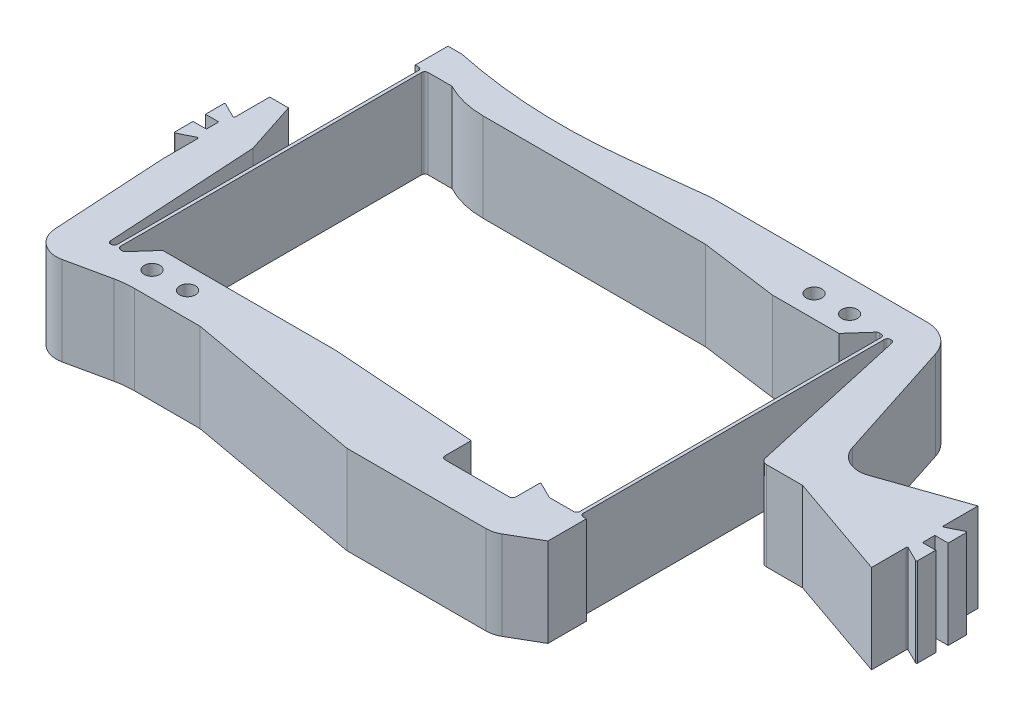
SolidWorks part; units mm, degrees
material "6061-O (SS)"
ref_plane "Front Plane" through (0, 0, 0) normal (0, 0, 1) x (1, 0, 0)
ref_plane "Top Plane" through (0, 0, 0) normal (0, 1, 0) x (1, 0, 0)
ref_plane "Right Plane" through (0, 0, 0) normal (1, 0, 0) x (0, 0, -1)
sketch "Sketch1" plane through (0, 0, 0) normal (0, 1, 0) x (1, 0, 0)
  line L1 (-76.2, 0) -> (76.2, 0) construction
  line L7 (0, 43.9941) -> (-76.2, 0) construction
  line L8 (76.2, 0) -> (0, 43.9941) construction
  line L9 (-43.0927, 22) -> (-43.0927, -22) construction
  line L10 (9.8199, -19.0502) -> (-29.8041, -19.0502)
  line L11 (9.8199, -19.0502) -> (9.8199, 19.0502)
  line L12 (9.8199, 19.0502) -> (-29.8041, 19.0502)
  line L13 (-29.8041, -19.0502) -> (-29.8041, 19.0502)
  line L14 (9.8199, -19.0502) -> (-29.8041, 19.0502) construction
  line L15 (9.8199, 19.0502) -> (-29.8041, -19.0502) construction
  line L16 (-29.8041, 19.0502) -> (-39.3291, 19.0502)
  line L17 (-29.8041, 19.0502) -> (-29.8041, -19.0502)
  line L18 (-29.8041, -19.0502) -> (-39.3291, -19.0502)
  line L19 (-39.3291, 19.0502) -> (-39.3291, -19.0502)
  line L20 (9.8199, -19.0502) -> (19.3449, -19.0502)
  line L21 (9.8199, -19.0502) -> (9.8199, 19.0502)
  line L22 (9.8199, 19.0502) -> (19.3449, 19.0502)
  line L23 (19.3449, -19.0502) -> (19.3449, 19.0502)
  line L24 (23.1085, 22) -> (23.1085, -22) construction
  line L25 (-43.3213, 22) -> (-43.3213, -22)
  line L26 (22.8799, 22) -> (22.8799, -22)
  line L27 (-42.8641, 22) -> (-42.8641, -22)
  line L28 (23.3371, 22) -> (23.3371, -22)
  line L29 (-42.8641, -5.4114) -> (-39.3291, -5.4114) construction
  line L30 (22.8799, -5.4114) -> (19.3449, -5.4114) construction
  line L31 (0, 0) -> (0, 43.9941) construction
  line L32 (-52.8845, 13.4612) -> (-51.8236, 31.3444) construction
  line L33 (-51.8236, 31.3444) -> (-30.0207, 26.6616) construction
  line L34 (-45.0888, 7.62) -> (-45.0888, -7.62) construction
  line L35 (-44.2357, 22) -> (-43.3213, 22)
  line L36 (-50.6866, 7.62) -> (-49.4633, 28.2396)
  line L37 (-49.4633, 28.2396) -> (-19.3998, 21.7826)
  line L38 (-49.4633, 28.2396) -> (-30.5541, 24.1783) construction
  line L39 (52.8845, 13.4612) -> (36.8667, 5.4384) construction
  line L40 (36.8667, 5.4384) -> (30.0207, 26.6616) construction
  line L41 (0, 43.9941) -> (-30.0207, 26.6616) construction
  line L42 (53.8514, 11.5308) -> (35.5843, 2.3813)
  line L43 (35.5843, 2.3813) -> (27.9659, 25.9988)
  line L44 (24.2515, 22) -> (28.7842, 23.4621) construction
  line L45 (35.5843, 2.3813) -> (35.5843, -2.3813) construction
  line L46 (-44.2357, 22) -> (-45.0888, 7.62)
  line L47 (-45.0888, -7.62) -> (-44.2357, -22)
  line L48 (-50.349, 13.3108) -> (-49.4633, 28.2396) construction
  line L49 (53.8514, -11.5308) -> (35.5843, -2.3813)
  line L50 (-43.3213, -22) -> (-44.2357, -22)
  line L52 (35.5843, -2.3813) -> (27.9659, -25.9988)
  line L53 (-49.4633, -28.2396) -> (-19.3998, -21.7826)
  line L54 (-50.6866, -7.62) -> (-49.4633, -28.2396)
  line L55 (23.3371, 22) -> (24.2515, 22)
  line L56 (76.2, 0) -> (0, -43.9941) construction
  line L57 (0, -43.9941) -> (-76.2, 0) construction
  line L58 (71.882, 0) -> (0, -41.5011)
  line L59 (0, -41.5011) -> (-71.882, 0)
  line L60 (0, 41.5011) -> (-71.882, 0)
  line L61 (71.882, 0) -> (0, 41.5011)
  line L62 (27.5523, -28.2396) -> (-2.5112, -21.7826)
  line L63 (27.5523, 28.2396) -> (-2.5112, 21.7826)
  circle A0 centre (-43.0927, 22) radius 4.7627 construction
  circle A3 centre (24.2515, 22) radius 4.7627 construction
  point P2 (0, 0)
  point P12 (-9.9921, 0)
  point P46 (35.5843, 0)
  point P47 (0, 43.9941)
  point P57 (0, 43.9941)
  point P64 (-45.0888, 0)
  point P70 (-43.3213, 0)
  point P77 (-10.9555, 0)
  dimension "D4" = 38.1004
  dimension "D5" = 39.624
  dimension "D6" = 9.525
  dimension "D7" = 44
  dimension "D8" = 150
  dimension "D13" = 1.7675
  dimension "D2" = 152.4
  dimension "D19" = 0.9144
  dimension "D14" = 5.588
  dimension "D15" = 15.24
  dimension "D3" = 4.7627
  dimension "D11" = 3.535
  dimension "D9" = 0.2286
  dimension "D18" = 2.159
  dimension "D17" = 2.159
  dimension "D16" = 2
  dimension "D20" = 2
sketch "Sketch2" plane through (0, 0, 0) normal (0, 1, 0) x (1, 0, 0)
  line L3 (-29.8041, -19.0502) -> (-29.8041, 19.0502) construction
  line L7 (9.8199, 19.0502) -> (19.3449, 19.0502)
  line L10 (-50.6806, 7.62) -> (-47.9942, 7.62)
  line L11 (-47.9942, 7.62) -> (-45.5383, 0.0647)
  line L12 (-45.5383, 0.0647) -> (-44.2357, -22)
  line L13 (-44.2357, -22) -> (-41.9497, -22)
  line L14 (-41.9497, -22) -> (-39.3291, -19.0502)
  line L24 (-30.1531, 24.0922) -> (-6.6386, 26.7627)
  line L25 (-39.3291, -19.0502) -> (-14.5241, -19.0502)
  line L26 (9.8199, -19.0502) -> (-29.8041, -19.0502) construction
  line L29 (9.8199, 19.0502) -> (-1.2291, 20.5502)
  line L30 (9.8199, 19.0502) -> (-29.8041, 19.0502) construction
  line L32 (16.4949, -22) -> (29.7221, -22) construction
  line L34 (71.882, 0) -> (0, -41.5011) construction
  line L36 (0, -41.5011) -> (-71.882, 0) construction
  line L37 (-34.5666, -6.7134) -> (-34.5666, -25.7742) construction
  line L38 (-37.9845, -25.7742) -> (-49.4633, -28.2396)
  line L39 (-49.4633, -28.2396) -> (-50.6806, -7.62)
  line L40 (-50.6806, -7.62) -> (-50.6806, 7.62)
  line L43 (-49.4633, 28.2396) -> (-19.3998, 21.7826) construction
  line L44 (-42.2453, 26.6893) -> (-30.1531, 24.0922)
  line L45 (0, 41.5011) -> (-71.882, 0) construction
  line L47 (28.7842, 23.4621) -> (35.5843, 2.3813)
  line L48 (35.5843, 2.3813) -> (50.6806, 7.62)
  line L49 (-6.6386, 26.7627) -> (24.2515, 26.7627)
  line L51 (-39.3291, -6.7134) -> (-29.8041, -6.7134) construction
  line L52 (50.6806, -7.62) -> (35.5843, -2.3813)
  line L53 (35.5843, -2.3813) -> (29.6871, -2.3813)
  line L54 (29.6871, -2.3813) -> (24.2515, 22)
  line L55 (24.2515, 22) -> (21.9655, 22)
  line L61 (19.2496, -30.3873) -> (-1.6246, -30.3873)
  line L64 (-1.2291, 20.5502) -> (-36.4963, 20.5502)
  line L68 (-42.2453, 26.6893) -> (-48.2113, 26.6893)
  line L69 (-1.6246, -30.3873) -> (-27.2398, -25.7742)
  line L70 (-38.9574, 22) -> (-36.4963, 20.5502)
  line L71 (16.4949, -22) -> (16.4949, -24.7993)
  line L73 (21.9655, 22) -> (19.3449, 19.0502)
  line L74 (16.4949, -24.7993) -> (6.3199, -24.7993)
  line L75 (6.3199, -24.7993) -> (6.3199, -20.5502)
  line L76 (6.3199, -20.5502) -> (-14.5241, -19.0502)
  line L77 (19.2496, -30.3873) -> (29.7221, -24.341)
  line L78 (9.8199, -19.0502) -> (12.9949, -19.0502) construction
  line L79 (9.8199, -19.0502) -> (9.8199, -23.7833) construction
  line L80 (9.8199, -23.7833) -> (12.9949, -23.7833) construction
  line L81 (12.9949, -19.0502) -> (12.9949, -23.7833) construction
  line L82 (29.7221, -24.341) -> (29.7221, -22)
  line L83 (0, 0) -> (0, 13.8808) construction
  line L84 (50.6806, -7.62) -> (50.6806, 7.62)
  line L85 (-37.9845, -25.7742) -> (-27.2398, -25.7742)
  line L86 (-39.3291, 19.0502) -> (-39.3291, -19.0502) construction
  line L87 (-49.4633, -28.2396) -> (-19.3998, -21.7826) construction
  line L90 (9.8199, 19.0502) -> (-29.8041, -19.0502) construction
  line L91 (-38.9574, 22) -> (-48.2113, 22)
  line L92 (-48.2113, 26.6893) -> (-48.2113, 22)
  line L95 (-76.2, 0) -> (76.2, 0) construction
  line L96 (16.4949, -22) -> (16.4949, -20.7842)
  line L97 (23.3371, 22) -> (23.3371, -22) construction
  line L99 (16.4949, -20.7842) -> (18.9624, -22)
  line L100 (29.7221, -22) -> (18.9624, -22)
  circle A0 centre (24.2515, 22) radius 4.7627 construction
  arc A1 (24.2515, 26.7627) -> (28.7842, 23.4621) centre (24.2515, 22) cw
  circle A2 centre (-41.9497, -22) radius 4.5227 construction
  circle A3 centre (-44.2357, -22) radius 5.5863 construction
  point P10 (23.1085, 22)
  point P19 (50.6806, 0)
  point P44 (-43.0927, -22)
  point P50 (23.1085, -22)
  point P51 (-9.9921, 0)
  point P112 (-9.9514, 0)
  dimension "D2" = 9.0453
  dimension "D4" = 11.1726
  dimension "D1" = 28.575
  dimension "D5" = 3.5
  dimension "D6" = 3.5
  dimension "D7" = 3.175
  dimension "D8" = 5.588
  dimension "D9" = 1.016
  dimension "D10" = 1.5
  dimension "D3" = 9.525
  dimension "D11" = 9.525
  dimension "D13" = 57.15
  dimension "D12" = 1.5
  dimension "D15" = 25.5194
  dimension "D14" = 2.4675
  dimension "D16" = 6.35
extrude "Boss-Extrude1" add sketch "Sketch2" along normal blind 6.35 and the other way blind 6.35
sketch "Sketch3" plane through (0, 0, 0) normal (0, 1, 0) x (1, 0, 0)
  line L0 (-42.8641, 22) -> (-42.8641, -22) construction
  line L1 (-42.8641, 22.508) -> (-43.3213, 22.508)
  line L2 (-42.8641, 22.508) -> (-42.8641, -22)
  line L3 (-42.8641, -22) -> (-43.3213, -22)
  line L4 (-43.3213, 22.508) -> (-43.3213, -22)
  line L5 (22.8799, -22) -> (23.3371, -22)
  line L6 (22.8799, -22) -> (22.8799, 22.508)
  line L7 (22.8799, 22.508) -> (23.3371, 22.508)
  line L8 (23.3371, -22) -> (23.3371, 22.508)
  line L9 (23.3371, 22) -> (23.3371, -22) construction
  line L10 (-48.2113, 22) -> (-38.9574, 22) construction
  dimension "D1" = 0.508
extrude "Boss-Extrude2" add sketch "Sketch3" along normal through all and the other way through all
sketch "Sketch7" plane through (0, 0, 0) normal (0, 1, 0) x (1, 0, 0)
  line L0 (-50.6806, 0) -> (-50.6806, 2.54) construction
  line L1 (-50.6806, 7.62) -> (-50.6806, -7.62) construction
  line L2 (-50.6806, 2.54) -> (-53.2206, 3.81) construction
  line L3 (-53.2206, 3.81) -> (-53.2206, -3.81) construction
  line L4 (-53.2206, -3.81) -> (-50.6806, -2.54) construction
  line L5 (-50.6806, -2.54) -> (-50.6806, 0) construction
  line L6 (0, 0) -> (0, 12.9706) construction
  line L7 (-76.2, 0) -> (76.2, 0) construction
  line L8 (0, 0) -> (0, 43.9941) construction
  line L14 (-53.1444, 3.6867) -> (-53.1444, -3.6867)
  line L15 (-53.1444, -3.6867) -> (-50.7568, -2.4929)
  line L16 (-50.7568, -2.4929) -> (-50.7568, 0) construction
  line L17 (-50.7568, 0) -> (-50.7568, 2.4929) construction
  line L18 (-50.7568, 2.4929) -> (-53.1444, 3.6867)
  line L19 (-50.7568, 2.4929) -> (-50.6806, 2.4548)
  line L20 (-50.6806, 2.4548) -> (-50.6806, -2.4548)
  line L21 (-50.6806, -2.4548) -> (-50.7568, -2.4929)
  line L22 (50.6806, 2.4548) -> (50.6806, -2.4548)
  line L23 (50.7568, 2.4929) -> (50.6806, 2.4548)
  line L24 (50.7568, 2.4929) -> (53.1444, 3.6867)
  line L25 (53.1444, 3.6867) -> (53.1444, -3.6867)
  line L26 (53.1444, -3.6867) -> (50.7568, -2.4929)
  line L27 (50.6806, -2.4548) -> (50.7568, -2.4929)
  dimension "D1" = 2.54
  dimension "D2" = 7.62
  dimension "D3" = 2.54
  dimension "D4" = 0.0762
extrude "Boss-Extrude4" add sketch "Sketch7" along normal through all and the other way through all
sketch "Sketch8" plane through (0, 6.35, 0) normal (0, 1, 0) x (1, 0, 0)
  line L0 (-76.2, 0) -> (76.2, 0) construction
  line L1 (-51.2394, -0.889) -> (-53.2714, -0.889)
  line L2 (-51.2394, -0.889) -> (-51.2394, 0.889)
  line L3 (-51.2394, 0.889) -> (-53.2714, 0.889)
  line L4 (-53.2714, -0.889) -> (-53.2714, 0.889)
  line L5 (-51.2394, -0.889) -> (-53.2714, 0.889) construction
  line L6 (-51.2394, 0.889) -> (-53.2714, -0.889) construction
  line L7 (-53.1444, 3.6867) -> (-53.1444, -3.6867) construction
  line L8 (0, 0) -> (0, 15.7634) construction
  line L9 (0, 0) -> (0, 43.9941) construction
  line L10 (51.2394, 0.889) -> (53.2714, -0.889) construction
  line L11 (51.2394, -0.889) -> (53.2714, 0.889) construction
  line L12 (53.2714, -0.889) -> (53.2714, 0.889)
  line L13 (51.2394, 0.889) -> (53.2714, 0.889)
  line L14 (51.2394, -0.889) -> (51.2394, 0.889)
  line L15 (51.2394, -0.889) -> (53.2714, -0.889)
  point P0 (-52.2554, 0)
  point P18 (52.2554, 0)
  dimension "D1" = 2.032
  dimension "D2" = 1.778
  dimension "D3" = 0.127
extrude "Cut-Extrude1" cut sketch "Sketch8" against normal through all
fillet "Fillet1" radius 0.4572 12 edges at (24.2515, 0, -22) (21.9655, 0, -22) (-41.9497, 0, 22) (-42.8641, 0, 22) (-44.2357, 0, 22) (-43.3213, 0, 22) (23.3371, 0, -22) (22.8799, 0, -22) (-42.8641, 0, -22) (-43.3213, 0, -22) (23.3371, 0, 22) (22.8799, 0, 22)
fillet "Fillet2" radius 0.9144 5 edges at (29.6871, 0, 2.3813) (29.7221, 0, 22) (29.7221, 0, 24.341) (-48.2113, 0, -26.6893) (-48.2113, 0, -22)
fillet "Fillet3" radius 3.556 3 edges at (35.5843, 0, -2.3813) (-49.4633, 0, 28.2396) (19.2496, 0, 30.3873)
fillet "Fillet6" radius 12.7 2 edges at (-36.4963, 0, -20.5502) (-37.9845, 0, 25.7742)
ref_axis "Axis2" through (0, 0, -43.9941) along (0, 1, 0)
pattern_circular "CirPattern3" [suppressed] count 3 over 360 about axis through (0, 0, -43.9941) along (0, 1, 0) of bodies 145 106
ref_axis "Axis3" through (-76.2, 0, 0) along (0, 1, 0)
pattern_circular "CirPattern4" [suppressed] count 3 over 360 about axis through (-76.2, 0, 0) along (0, 1, 0) of bodies 111 145 112 106
ref_plane "Plane1" [suppressed] through (-76.2, 0, 0) normal (1, 0, 0) x (0, 0, -1)
mirror "Mirror3" [suppressed] about plane through (0, 0, 0) normal (0, 0, 1) of bodies 113 111
ref_plane "Plane2" [suppressed] through (0, 0, 131.9823) normal (0, 0, 1) x (1, 0, 0)
mirror "Mirror4" [suppressed] about plane through (0, 0, 131.9823) normal (0, 0, 1) of bodies 113 115 112 111 117 145 131 116 118 132 106
sketch "Sketch9" plane through (0, 6.35, 0) normal (0, 1, 0) x (1, 0, 0)
  line L0 (-37.6781, -22.2252) -> (-32.5981, -22.2252) construction
  line L1 (12.6139, 22.2252) -> (17.6939, 22.2252) construction
  line L2 (9.8199, 19.0502) -> (19.3449, 19.0502) construction
  line L3 (9.8199, -19.0502) -> (9.8199, 19.0502) construction
  line L4 (-29.8041, -19.0502) -> (-29.8041, 19.0502) construction
  line L5 (-29.8041, -19.0502) -> (-39.3291, -19.0502) construction
  circle A0 centre (-37.6781, -22.2252) radius 1.1303
  circle A1 centre (-32.5981, -22.2252) radius 1.1303
  circle A2 centre (12.6139, 22.2252) radius 1.1303
  circle A3 centre (17.6939, 22.2252) radius 1.1303
  dimension "D3" = 2.2606
  dimension "D1" = 3.175
  dimension "D2" = 5.08
  dimension "D4" = 2.794
  dimension "D5" = 2.794
  dimension "D6" = 3.175
extrude "Cut-Extrude2" cut sketch "Sketch9" against normal through all
fillet "Fillet7" radius 0.127 1 edges at (16.4949, 0, 20.7842)
fillet "Fillet8" radius 0.508 2 edges at (6.3199, 0, 24.7993) (16.4949, 0, 24.7993)
fillet "Fillet9" radius 76.2 1 edges at (-30.1531, 0, -24.0922)
sketch "Sketch10" plane through (0, 6.35, 0) normal (0, 1, 0) x (1, 0, 0)
  line L0 (12.3091, -61.2047) -> (59.1594, 19.9424)
  line L1 (12.3091, -61.2047) -> (-59.1594, -19.9424)
  line L2 (59.1594, 19.9424) -> (-12.3091, 61.2047)
  line L3 (-59.1594, -19.9424) -> (-12.3091, 61.2047)
  line L4 (12.3091, -61.2047) -> (-12.3091, 61.2047) construction
  line L5 (59.1594, 19.9424) -> (-59.1594, -19.9424) construction
  line L6 (0, 0) -> (17.1685, 0) construction
  point P1 (0, 0)
  dimension "D1" = 93.7006
  dimension "D2" = 82.5246
  dimension "D3" = 60
sketch "Sketch11" plane through (0, 6.35, 0) normal (0, 1, 0) x (1, 0, 0)
  line L1 (47.625, 15.875) -> (-47.625, 15.875)
  line L2 (47.625, 15.875) -> (47.625, -15.875)
  line L3 (47.625, -15.875) -> (-47.625, -15.875)
  line L4 (-47.625, 15.875) -> (-47.625, -15.875)
  line L5 (47.625, 15.875) -> (-47.625, -15.875) construction
  line L6 (47.625, -15.875) -> (-47.625, 15.875) construction
  point P0 (0, 0)
  dimension "D1" = 95.25
  dimension "D2" = 31.75
sketch "Sketch12" plane through (0, 6.35, 0) normal (0, 1, 0) x (1, 0, 0)
  line L0 (-48.2113, 25.7749) -> (-48.2113, 22.9144) construction
  line L1 (-44.2357, 22) -> (-48.2113, 22)
  line L2 (-44.2357, 22) -> (-44.2357, 26.6893)
  line L3 (-44.2357, 26.6893) -> (-48.2113, 26.6893)
  line L4 (-48.2113, 22) -> (-48.2113, 26.6893)
  line L5 (-44.2357, 22) -> (-48.2113, 26.6893) construction
  line L6 (-44.2357, 26.6893) -> (-48.2113, 22) construction
  line L7 (-47.2969, 22) -> (-43.7785, 22) construction
  line L8 (-42.2453, 26.6893) -> (-47.2969, 26.6893) construction
  line L9 (-43.3213, 21.5428) -> (-43.3213, -21.5428) construction
  line L10 (28.8077, -22) -> (23.7943, -22) construction
  line L11 (29.7221, -30.3873) -> (24.2515, -30.3873)
  line L12 (29.7221, -30.3873) -> (29.7221, -22)
  line L13 (29.7221, -22) -> (24.2515, -22)
  line L14 (24.2515, -30.3873) -> (24.2515, -22)
  line L15 (29.7221, -30.3873) -> (24.2515, -22) construction
  line L16 (29.7221, -22) -> (24.2515, -30.3873) construction
  line L17 (29.7221, -23.8131) -> (29.7221, -22.9144) construction
  line L18 (23.3371, -21.5428) -> (23.3371, 21.5428) construction
  line L19 (-1.6246, -30.3873) -> (18.2968, -30.3873) construction
  point P0 (-46.2235, 24.3446)
  point P15 (26.9868, -26.1937)
  dimension "D1" = 0.9144
  dimension "D2" = 0.9144
extrude "Cut-Extrude3" cut sketch "Sketch12" against normal through all
fillet "Fillet10" radius 0.127 8 edges at (-50.6806, 0, -2.4548) (-50.6806, 0, 2.4548) (-53.1444, 0, 3.6867) (-53.1444, 0, -3.6867) (53.1444, 0, -3.6867) (50.6806, 0, -2.4548) (53.1444, 0, 3.6867) (50.6806, 0, 2.4548)
equation "\"thk_mount\"= 0.375in"
equation "\"D6@Sketch1\"=\"thk_mount\""
equation "\"D9@Sketch1\"=\"D10@Sketch1\""
equation "\"tk_flex\"= 0.018in"
equation "\"D10@Sketch1\"=\"tk_flex\"/2"
equation "\"lg_link\"= 6in"
equation "\"dx\"= 3.5mm"
equation "\"D2@Sketch1\"=\"lg_link\""
equation "\"D19@Sketch1\"=\"tk_flex\"*2"
equation "\"tk_plate\"=0.5in"
equation "\"D1@Boss-Extrude1\"=\"tk_plate\"/2"
equation "\"D2@Boss-Extrude1\"=\"tk_plate\"/2"
equation "\"D5@Sketch2\"=\"dx\""
equation "\"D6@Sketch2\"=\"dx\""
equation "\"D1@Fillet2\"=\"tk_flex\"*2"
equation "\"D11@Sketch2\"=\"D3@Sketch2\""
equation "\"D12@Sketch2\"=1.5mm"
equation "\"D1@Fillet1\"=\"tk_flex\""
equation "\"D11@Sketch1\"=\"dx\"*1.01"
equation "\"D13@Sketch1\"=\"dx\"*.505"
